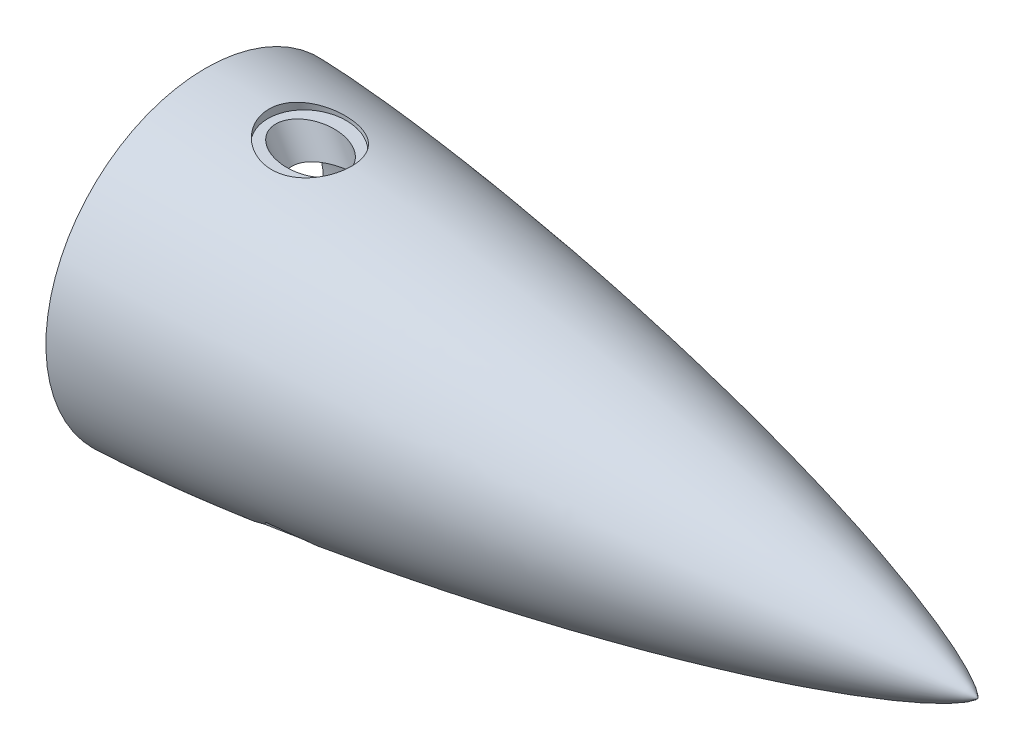
SolidWorks part; units mm, degrees
material "ABS"
ref_plane "Front Plane" through (0, 0, 0) normal (0, 0, 1) x (1, 0, 0)
ref_plane "Top Plane" through (0, 0, 0) normal (0, 1, 0) x (1, 0, 0)
ref_plane "Right Plane" through (0, 0, 0) normal (1, 0, 0) x (0, 0, -1)
ref_axis "Axis1" through (444.767, 0, 0) along (-1, 0, 0)
sketch "Sketch10" plane through (0, 0, 0) normal (0, 0, 1) x (1, 0, 0)
  line L1 (-0.5188, 0) -> (486.9547, 0) construction
  line L2 (0.3953, 69.55) -> (0.3953, 64.55)
  line L3 (0.3953, 62.55) -> (136.931, 62.55)
  line L4 (409.4812, 0) -> (389.4812, 0)
  line L5 (0.3953, 64.55) -> (0.3953, 62.55)
  line L7 (0.3953, 69.55) -> (0.3953, 84.55)
  line L9 (444.767, 0) -> (-98.162, 0) construction
  spline S0 degree 4 poles (409.4812, 0) (409.4788, 0.0135) (409.4718, 0.0399) (409.45, 0.0903) (409.4052, 0.1736) (409.3386, 0.2747) (409.2332, 0.4144) (409.0715, 0.6026) (408.8144, 0.8684) (408.376, 1.2687) (407.6237, 1.874) (406.3009, 2.8069) (403.9508, 4.2541) (399.8003, 6.4739) (392.937, 9.6599) (381.0889, 14.4581) (364.0279, 20.4397) (342.5658, 27.076) (317.7374, 33.9485) (292.1491, 40.4025) (266.444, 46.3727) (240.6453, 51.9227) (214.7673, 57.0897) (188.82, 61.8964) (166.0615, 65.7958) (146.5183, 68.9193) (130.2092, 71.3728) (117.1484, 73.2437) (104.0744, 75.0198) (92.6232, 76.4872) (82.7998, 77.6794) (74.6082, 78.627) (68.0516, 79.3563) (61.4918, 80.0556) (54.9286, 80.7233) (48.3622, 81.3575) (41.7923, 81.956) (36.0408, 82.4459) (31.1087, 82.8394) (26.9972, 83.1482) (23.7071, 83.3831) (20.0917, 83.6266) (16.7244, 83.837) (13.6055, 84.0163) (10.7352, 84.1667) (8.4384, 84.2771) (6.1411, 84.3768) (4.1305, 84.4519) (2.4068, 84.5068) (1.2575, 84.5344) (0.6827, 84.5468) (0.3953, 84.55) knots 0 0 0 0 0 0.00013 0.00026 0.00052 0.0009 0.00128 0.001925 0.002882 0.004418 0.006927 0.011111 0.018279 0.030673 0.051704 0.083102 0.139909 0.202703 0.265496 0.32829 0.391083 0.453877 0.516671 0.579464 0.642258 0.673655 0.705051 0.736448 0.767845 0.799242 0.81494 0.830639 0.846337 0.862036 0.877734 0.893432 0.909131 0.924829 0.932678 0.940527 0.948377 0.956226 0.967169 0.972641 0.978113 0.983585 0.989056 0.994528 0.997264 1 1 1 1 1 construction
  spline S1 degree 4 poles (409.4812, 0) (409.4788, 0.0135) (409.4718, 0.0399) (409.45, 0.0903) (409.4052, 0.1736) (409.3386, 0.2747) (409.2332, 0.4144) (409.0715, 0.6026) (408.8144, 0.8684) (408.376, 1.2687) (407.6237, 1.874) (406.3009, 2.8069) (403.9508, 4.2541) (399.8003, 6.4739) (392.937, 9.6599) (381.0889, 14.4581) (364.0279, 20.4397) (342.5658, 27.076) (317.7374, 33.9485) (292.1491, 40.4025) (266.444, 46.3727) (240.6453, 51.9227) (214.7673, 57.0897) (188.82, 61.8964) (166.0615, 65.7958) (146.5183, 68.9193) (130.2092, 71.3728) (117.1484, 73.2437) (104.0744, 75.0198) (92.6232, 76.4872) (82.7998, 77.6794) (74.6082, 78.627) (68.0516, 79.3563) (61.4918, 80.0556) (54.9286, 80.7233) (48.3622, 81.3575) (41.7923, 81.956) (36.0408, 82.4459) (31.1087, 82.8394) (26.9972, 83.1482) (23.7071, 83.3831) (20.0917, 83.6266) (16.7244, 83.837) (13.6055, 84.0163) (10.7352, 84.1667) (8.4384, 84.2771) (6.1411, 84.3768) (4.1305, 84.4519) (2.4068, 84.5068) (1.2575, 84.5344) (0.6827, 84.5468) (0.3953, 84.55) knots 0 0 0 0 0 0.00013 0.00026 0.00052 0.0009 0.00128 0.001925 0.002882 0.004418 0.006927 0.011111 0.018279 0.030673 0.051704 0.083102 0.139909 0.202703 0.265496 0.32829 0.391083 0.453877 0.516671 0.579464 0.642258 0.673655 0.705051 0.736448 0.767845 0.799242 0.81494 0.830639 0.846337 0.862036 0.877734 0.893432 0.909131 0.924829 0.932678 0.940527 0.948377 0.956226 0.967169 0.972641 0.978113 0.983585 0.989056 0.994528 0.997264 1 1 1 1 1
  spline S2 degree 4 poles (389.4812, 0) (389.479, 0.0123) (389.4724, 0.0363) (389.4524, 0.0822) (389.412, 0.1569) (389.3528, 0.2469) (389.2596, 0.3707) (389.116, 0.5387) (388.8856, 0.7778) (388.4915, 1.1386) (387.8126, 1.6854) (386.6208, 2.5252) (384.5016, 3.8269) (380.7799, 5.8078) (374.6778, 8.6215) (364.2011, 12.8293) (349.1637, 18.0457) (330.2743, 23.8076) (308.4217, 29.7544) (285.9004, 35.3204) (263.2763, 40.4518) (240.5702, 45.2052) (217.7948, 49.6139) (194.959, 53.6981) (174.9303, 56.9957) (157.7317, 59.6247) (143.3798, 61.6809) (131.8866, 63.2429) (120.3822, 64.7193) (110.3061, 65.9329) (101.6625, 66.9139) (94.4549, 67.6898) (88.6861, 68.2846) (82.9146, 68.8522) (77.1403, 69.3912) (71.3632, 69.9) (65.5834, 70.3763) (60.5237, 70.7625) (56.185, 71.0696) (52.5683, 71.3081) (49.6742, 71.4878) (46.5171, 71.6708) (43.0969, 71.8518) (39.9065, 72.0008) (36.946, 72.119) (34.4784, 72.2017) (32.7508, 72.2492) (31.2698, 72.2816) (30.2823, 72.2953) (29.7885, 72.301) (29.5416, 72.3012) knots 0 0 0 0 0 0.000135 0.00027 0.00054 0.00092 0.001299 0.001947 0.002931 0.004512 0.007081 0.01138 0.018708 0.031424 0.052705 0.084103 0.14091 0.203703 0.266497 0.329291 0.392084 0.454878 0.517672 0.580465 0.643259 0.674656 0.706052 0.737449 0.768846 0.800243 0.815941 0.831639 0.847338 0.863036 0.878735 0.894433 0.910132 0.92583 0.933679 0.941528 0.949378 0.957227 0.96792 0.978613 0.98396 0.989307 0.994653 0.997327 1 1 1 1 1 construction
  spline S3 degree 4 poles (389.4812, 0) (389.479, 0.0123) (389.4724, 0.0363) (389.4524, 0.0822) (389.412, 0.1569) (389.3528, 0.2469) (389.2596, 0.3707) (389.116, 0.5387) (388.8856, 0.7778) (388.4915, 1.1386) (387.8126, 1.6854) (386.6208, 2.5252) (384.5016, 3.8269) (380.7799, 5.8078) (374.6778, 8.6215) (364.2011, 12.8293) (349.1637, 18.0457) (330.2743, 23.8076) (308.4217, 29.7544) (285.9004, 35.3204) (263.2763, 40.4518) (240.5702, 45.2052) (217.7948, 49.6139) (194.959, 53.6981) (174.9303, 56.9957) (157.7317, 59.6247) (146.075, 61.2947) (140.155, 62.1129) (137.1063, 62.5263) (136.931, 62.55) knots 0 0 0 0 0 0.000135 0.00027 0.00054 0.00092 0.001299 0.001947 0.002931 0.004512 0.007081 0.01138 0.018708 0.031424 0.052705 0.084103 0.14091 0.203703 0.266497 0.329291 0.392084 0.454878 0.517672 0.580465 0.643259 0.674656 0.706052 0.707968 0.707968 0.707968 0.707968 0.707968
  dimension "D1" = 84.55
  dimension "D3" = 410
  dimension "D5" = 390
  dimension "D2" = 15
revolve "Revolve1" add sketch "Sketch10" angle 360 about axis through (444.767, 0, 0) along (-1, 0, 0)
ref_plane "Plane3" through (0, 82.55, 0) normal (0, 1, 0) x (1, 0, 0)
sketch "Sketch20" plane through (0, 82.55, 0) normal (0, 1, 0) x (1, 0, 0)
  line L0 (444.767, 0) -> (-98.162, 0) construction
  line L1 (24.7702, 25) -> (64.7702, 25)
  line L2 (24.7702, 25) -> (24.7702, -15)
  line L3 (24.7702, -15) -> (64.7702, -15)
  line L4 (64.7702, 25) -> (64.7702, -15)
  line L5 (24.7702, 25) -> (64.7702, -15) construction
  line L6 (24.7702, -15) -> (64.7702, 25) construction
  point P4 (44.7702, 5)
  dimension "D1" = 40
  dimension "D2" = 15
  dimension "D3" = 40
extrude "Cut-Extrude3" [suppressed] cut sketch "Sketch20" along normal blind 12
sketch "Sketch22" plane through (0, 82.55, 0) normal (0, 1, 0) x (1, 0, 0)
  circle A0 centre (32, 6) radius 7.5
  dimension "D1" = 15
extrude "Cut-Extrude4" [suppressed] cut sketch "Sketch22" along normal through all
sketch "Sketch24" plane through (0, 82.55, 0) normal (0, 1, 0) x (1, 0, 0)
  line L0 (38.1988, 66.2764) -> (38.1988, 16.8548) construction
ref_plane "Plane4" through (-26.1955, 45.3719, 0) normal (-0.5, 0.866, 0) x (0, 0, 1)
sketch "Sketch26" plane through (-26.1955, 45.3719, 0) normal (-0.5, 0.866, 0) x (0, 0, 1)
  line L1 (-66.2764, 74.3561) -> (-16.8548, 74.3561) construction
  circle A0 centre (0, 86.3561) radius 15
  dimension "D1" = 12
extrude "Cut-Extrude5" cut sketch "Sketch26" against normal blind 50
ref_plane "Plane5" through (8.9989, 85.619, 0) normal (0.1045, 0.9945, 0) x (0, 0, 1)
sketch "Sketch30" plane through (8.9989, 85.619, 0) normal (0.1045, 0.9945, 0) x (0, 0, 1)
  line L0 (0, 442.3305) -> (0, -97.6242) construction
  circle A0 centre (0, 47.1511) radius 22
extrude "Cut-Extrude10" cut sketch "Sketch30" against normal blind 5
hole_wizard "Tap Drill for 1/4 Helicoil1" positions "Sketch31" profile "Sketch32" hole size "1/4-20" standard "ANSI Inch"
sketch "Sketch31" plane through (0.3953, 0, 0) normal (-1, 0, 0) x (0, 0, 1)
  line L1 (0, 0) -> (0, 69.55)
  circle A1 centre (0, 0) radius 69.55
  circle A2 centre (0, 0) radius 84.55 construction
  point P0 (-220.8452, 298.3381)
  point P23 (0, 69.55)
  dimension "D1" = 15
sketch "Sketch32" plane through (0.3953, 298.3381, -220.8452) normal (0, 1, 0) x (0, 0, 1)
  line L0 (0, 0) -> (0, 20)
  line L1 (0, 20) -> (3.3782, 20)
  line L2 (3.3782, 20) -> (3.3782, 0)
  line L5 (3.3782, 0) -> (0, 0)
  line L10 (0, 20) -> (-3.3782, 20) construction
  line L11 (0, -6.35) -> (0, 107.95) construction
  dimension "Hole Dia." = 6.7564
  dimension "Hole Depth" = 20
  dimension "Drill Angle" = 180
pattern_circular "CirPattern1" count 6 over 360 about axis through (444.767, 0, 0) along (-1, 0, 0) of "Tap Drill for 1/4 Helicoil1"
equation "\"TubeDiameter\" = 6.500in"
equation "\"D1@Sketch10\"=\"TubeDiameter\"/2mm+2mm"
equation "\"D1@Plane3\"=\"TubeDiameter\"/2mm"
